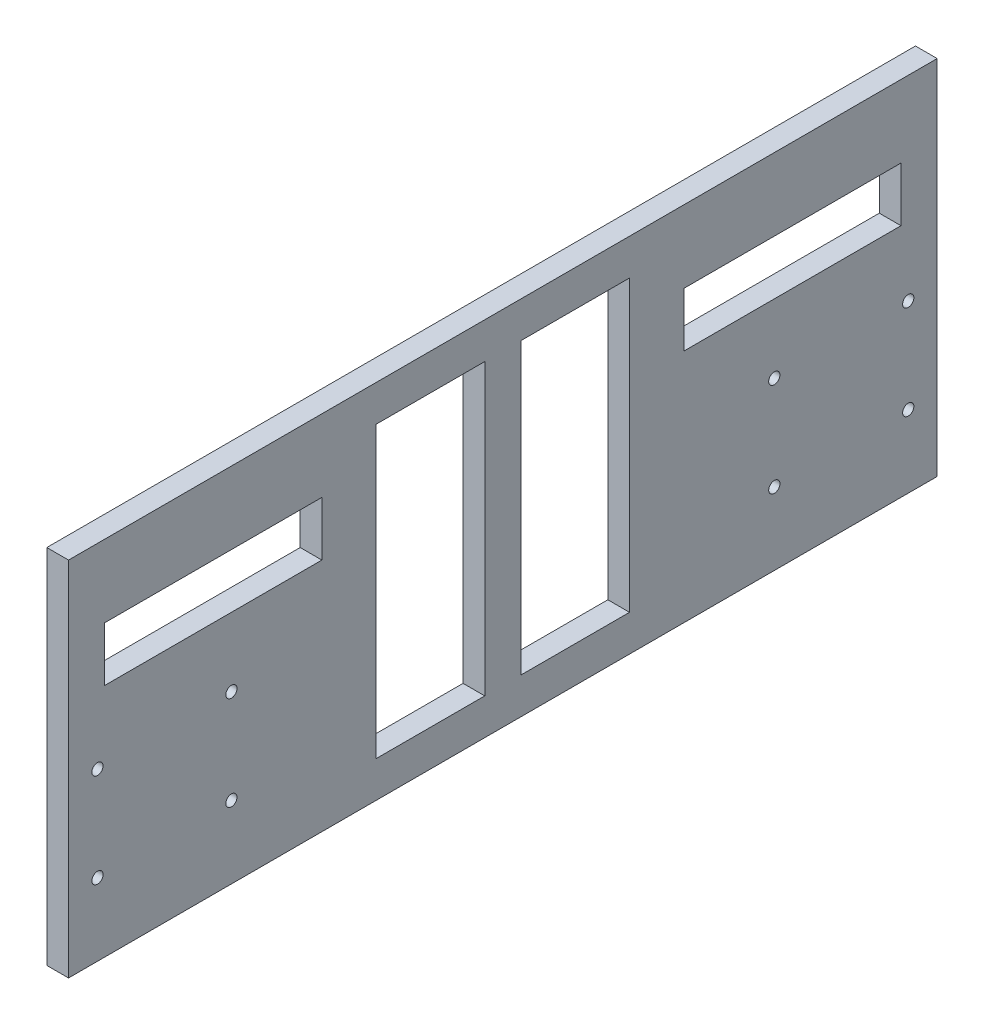
SolidWorks part; units mm, degrees
ref_plane "前视基准面" through (0, 0, 0) normal (0, 0, 1) x (1, 0, 0)
ref_plane "上视基准面" through (0, 0, 0) normal (0, 1, 0) x (1, 0, 0)
ref_plane "右视基准面" through (0, 0, 0) normal (1, 0, 0) x (0, 0, -1)
sketch "草图1" plane through (0, 0, 0) normal (1, 0, 0) x (0, 0, -1)
  line L1 (0, 0) -> (240, 0)
  line L2 (0, 0) -> (0, -100)
  line L3 (0, -100) -> (240, -100)
  line L4 (240, 0) -> (240, -100)
  dimension "D1" = 240
  dimension "D2" = 100
extrude "凸台-拉伸1" add sketch "草图1" along normal blind 6
sketch "草图2" plane through (6, 0, 0) normal (1, 0, 0) x (0, 0, -1)
  line L0 (0, 0) -> (0, -100) construction
  line L1 (8, -54) -> (45, -54) construction
  line L2 (8, -54) -> (8, -80) construction
  line L3 (8, -80) -> (45, -80) construction
  line L4 (45, -54) -> (45, -80) construction
  line L5 (240, 0) -> (0, 0) construction
  line L6 (120, 0) -> (120, -100) construction
  line L7 (0, -100) -> (240, -100) construction
  line L8 (195, -54) -> (195, -80) construction
  line L9 (232, -80) -> (195, -80) construction
  line L10 (232, -54) -> (232, -80) construction
  line L11 (232, -54) -> (195, -54) construction
  circle A0 centre (8, -54) radius 1.55
  circle A1 centre (45, -80) radius 1.55
  circle A2 centre (45, -54) radius 1.55
  circle A3 centre (8, -80) radius 1.55
  circle A4 centre (232, -80) radius 1.55
  circle A5 centre (195, -54) radius 1.55
  circle A6 centre (195, -80) radius 1.55
  circle A7 centre (232, -54) radius 1.55
  dimension "D5" = 3.1
  dimension "D1" = 8
  dimension "D2" = 54
  dimension "D3" = 37
  dimension "D4" = 26
extrude "切除-拉伸1" cut sketch "草图2" against normal through all
sketch "草图3" plane through (6, 0, 0) normal (1, 0, 0) x (0, 0, -1)
  line L0 (120, 0) -> (120, -100) construction
  line L1 (10, -20) -> (70, -20)
  line L2 (10, -20) -> (10, -35)
  line L3 (10, -35) -> (70, -35)
  line L4 (70, -20) -> (70, -35)
  line L5 (240, 0) -> (0, 0) construction
  line L6 (0, -100) -> (240, -100) construction
  line L7 (0, 0) -> (0, -100) construction
  line L8 (170, -20) -> (170, -35)
  line L9 (230, -35) -> (170, -35)
  line L10 (230, -20) -> (230, -35)
  line L11 (230, -20) -> (170, -20)
  dimension "D1" = 10
  dimension "D2" = 20
  dimension "D3" = 15
  dimension "D4" = 60
extrude "切除-拉伸2" cut sketch "草图3" against normal through all
sketch "草图4" plane through (6, 0, 0) normal (1, 0, 0) x (0, 0, -1)
  line L0 (120, 0) -> (120, -100) construction
  line L1 (85, -10) -> (115, -10)
  line L2 (85, -10) -> (85, -90)
  line L3 (85, -90) -> (115, -90)
  line L4 (115, -10) -> (115, -90)
  line L5 (240, 0) -> (0, 0) construction
  line L6 (0, -100) -> (240, -100) construction
  line L7 (0, 0) -> (0, -100) construction
  line L8 (125, -10) -> (125, -90)
  line L9 (155, -90) -> (125, -90)
  line L10 (155, -10) -> (155, -90)
  line L11 (155, -10) -> (125, -10)
  dimension "D1" = 10
  dimension "D2" = 10
  dimension "D3" = 85
  dimension "D4" = 30
extrude "切除-拉伸3" cut sketch "草图4" against normal through all contours L4 L1 L2 L3 | L8 L9 L10 L11 region at (6, -50, -100)
sketch "草图5" plane through (0, 0, 0) normal (-1, 0, 0) x (0, 0, 1)
  circle A0 centre (-195, -80) radius 3
  circle A1 centre (-232, -80) radius 3
  circle A2 centre (-195, -54) radius 3
  circle A3 centre (-232, -54) radius 3
  circle A4 centre (-45, -80) radius 3
  circle A5 centre (-8, -80) radius 3
  circle A6 centre (-8, -54) radius 3
  circle A7 centre (-45, -54) radius 3
  dimension "D1" = 6
extrude "切除-拉伸4" [suppressed] cut sketch "草图5" against normal blind 3
